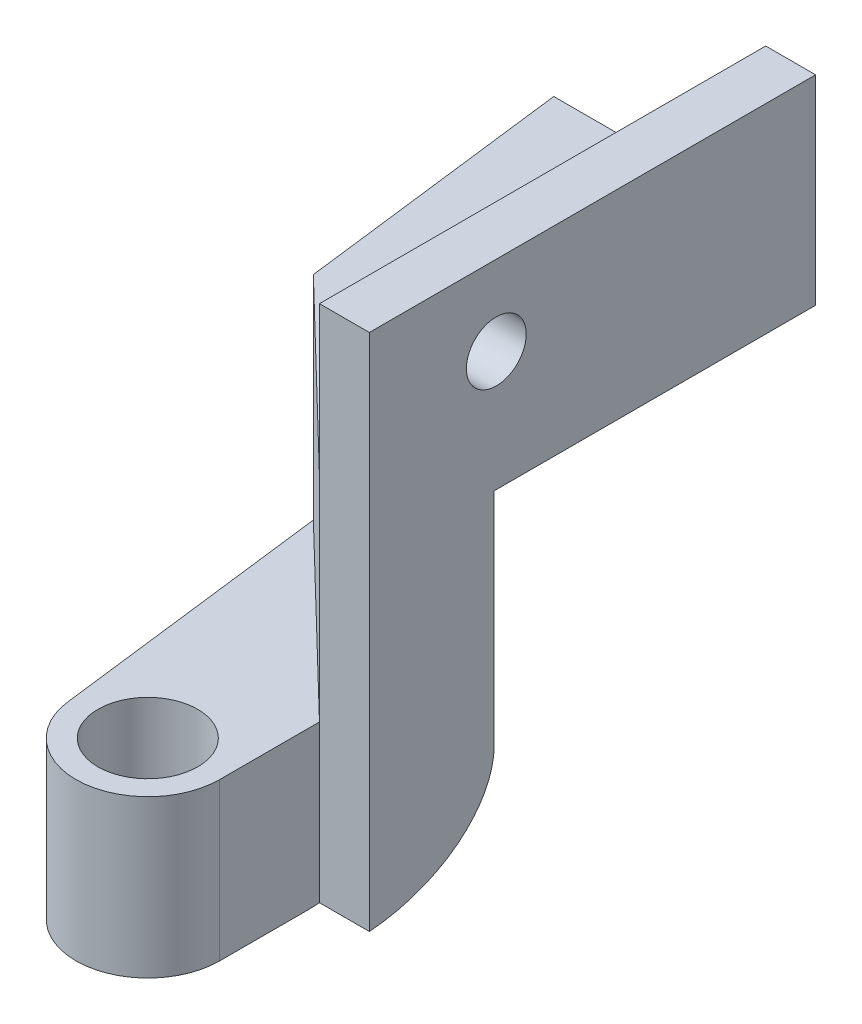
SolidWorks part; units mm, degrees
ref_plane "Front Plane" through (0, 0, 0) normal (0, 0, 1) x (1, 0, 0)
ref_plane "Top Plane" through (0, 0, 0) normal (0, 1, 0) x (1, 0, 0)
ref_plane "Right Plane" through (0, 0, 0) normal (1, 0, 0) x (0, 0, -1)
sketch "Croquis1" plane through (0, 0, 0) normal (0, 1, 0) x (1, 0, 0)
  line L3 (-7.02, 27.36) -> (-3.5726, -0.443)
  line L4 (3.6, 0) -> (3.6, 27.36)
  line L5 (3.6, 27.36) -> (-7.02, 27.36)
  line L6 (-5.315, 13.6091) -> (3.6, 5)
  line L7 (0, 0) -> (-2.5, 0) construction
  line L8 (-6.1962, 20.7158) -> (3.6, 11.2557)
  arc A3 (-3.5726, -0.443) -> (3.6, 0) centre (0, 0) ccw
  circle A4 centre (0, 0) radius 2.5
  circle A5 centre (-0.4, 21.36) radius 1.5
  point P13 (0, 0)
  point P15 (-4.9057, 10.3044)
  point P16 (3.6, 5)
  point P17 (0, 0)
  point P18 (3.6, 13.7377)
  point P19 (0, 0)
  point P21 (0, 0)
  dimension "D1" = 3.6
  dimension "D6" = 5
  dimension "D10" = 3
  dimension "D2" = 27.36
  dimension "D3" = 27.803
  dimension "D4" = 10.62
  dimension "D5" = 27.36
  dimension "D7" = 44
  dimension "D8" = 5
  dimension "D9" = 4.5
  dimension "D11" = 6
  dimension "D12" = 4
extrude "Saliente-Extruir1" add sketch "Croquis1" against normal blind 2.5 contours L3 L8 L4 L5 A5 | L8 L3 L6 L4 region at (-1.71, 0, -27.1671) region at (-1.0812, 0, -12.6976)
extrude "Saliente-Extruir2" add sketch "Croquis1<4>" against normal blind 7.87 from offset 10.65 separate body contours L3 A3 L4 L6 A4 region at (-1.0194, 0, -4.5744) offset against normal yes
sketch "Croquis1<4>" plane through (0, 0, 0) normal (0, 1, 0) x (1, 0, 0) same geometry as "Croquis1"
extrude "Saliente-Extruir3" add sketch "Croquis1<5>" against normal up to surface (18.52 mm away) contours L8 L3 L6 L4 region at (-1.0812, 0, -12.6976) up to face at (0, -18.52, 2.5)
sketch "Croquis1<5>" plane through (0, 0, 0) normal (0, 1, 0) x (1, 0, 0) same geometry as "Croquis1"
fillet "Redondeo1" radius 5 1 edges at (-1.2981, -18.52, -15.9858)
sketch "Croquis3" plane through (3.6, 0, 0) normal (1, 0, 0) x (0, 0, -1)
  line L0 (5, -10.65) -> (5, -18.4949)
  line L1 (27.36, 7.5) -> (5, 7.5)
  line L8 (0, -18.52) -> (4.3049, -18.52)
  line L9 (11.2557, -13.52) -> (11.2557, -2.5)
  line L10 (11.2557, -2.5) -> (27.36, -2.5)
  line L11 (27.36, -2.5) -> (27.36, 0)
  line L12 (27.36, 0) -> (5, 0)
  line L13 (5, 0) -> (5, -10.65)
  line L14 (5, -10.65) -> (0, -10.65)
  line L15 (0, -10.65) -> (0, -18.52)
  line L16 (0, -18.52) -> (4.3049, -18.52)
  line L17 (11.2557, -13.52) -> (11.2557, -2.5)
  line L18 (11.2557, -2.5) -> (27.36, -2.5)
  line L19 (27.36, -2.5) -> (27.36, 7.5)
  line L21 (5, 7.5) -> (5, -10.65)
  line L22 (5, -10.65) -> (0, -10.65)
  line L23 (0, -10.65) -> (0, -18.52)
  circle A0 centre (11.36, 3.5) radius 1.5
  ellipse E1 centre (4.3049, -13.52) end of major axis (11.2557, -13.52) minor radius 5 (4.3049, -18.52) -> (11.2557, -13.52) ccw
  ellipse E2 centre (4.3049, -13.52) end of major axis (11.2557, -13.52) minor radius 5 (4.3049, -18.52) -> (11.2557, -13.52) ccw
  point P25 (11.313, 3.7124)
  ellipse M2 centre (4.3049, -13.52) end of major axis (11.2557, -13.52) minor radius 5 (4.3049, -18.52) -> (11.2557, -13.52) ccw
  line M3 (11.2557, -13.52) -> (11.2557, -2.5)
  line M4 (11.2557, -2.5) -> (27.36, -2.5)
  line M5 (27.36, -2.5) -> (27.36, 0)
  line M6 (27.36, 0) -> (5, 0)
  line M7 (5, 0) -> (5, -10.65)
  dimension "D5" = 3
  dimension "D2" = 10
  dimension "D3" = 16
  dimension "D4" = 4
  dimension "D1" = 0
extrude "Saliente-Extruir4" add sketch "Croquis3" along normal blind 2.5 contours L0 M7 M2 M3 M4 M5 M6 | L1 L21 L19 A0 M6 region at (3.6, -6.6826, -11.0764) region at (3.6, 3.761, -16.3921)
equation "\"D1@Saliente-Extruir2\"=7.87"
